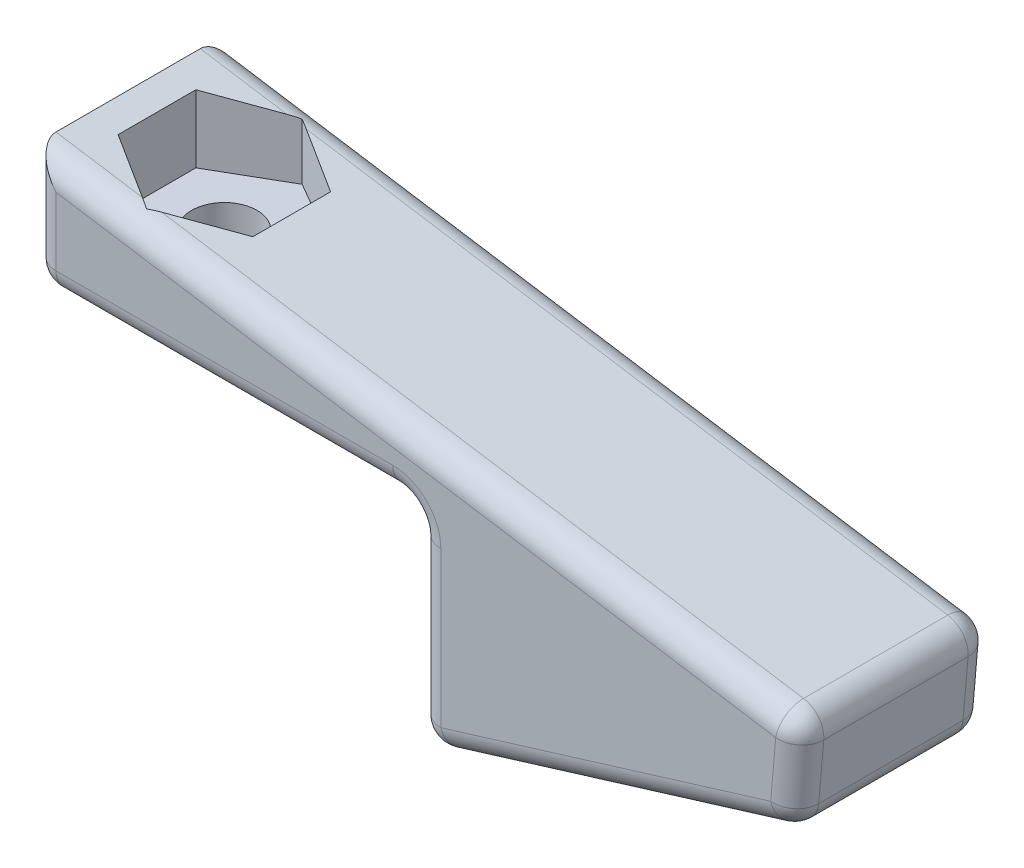
SolidWorks part; units mm, degrees
ref_plane "Front Plane" through (0, 0, 0) normal (0, 0, 1) x (1, 0, 0)
ref_plane "Top Plane" through (0, 0, 0) normal (0, 1, 0) x (1, 0, 0)
ref_plane "Right Plane" through (0, 0, 0) normal (1, 0, 0) x (0, 0, -1)
sketch "Sketch1" plane through (0, 0, 0) normal (0, 0, 1) x (1, 0, 0)
  line L0 (0, 0) -> (0, 7.9375)
  line L1 (0, 7.9375) -> (25.4, 3.9687)
  line L3 (50.2444, -6.35) -> (25.4, -13.97)
  line L4 (25.4, -13.97) -> (25.4, 0)
  line L5 (25.4, 0) -> (0, 0)
  line L6 (50.8, 0) -> (50.2444, -6.35)
  line L7 (50.8, 0) -> (25.4, 3.9687)
  point P3 (50.8, -1.5875)
  point P4 (49.4929, -7.9375)
  point P9 (0, 0)
  point P11 (0, 0)
  dimension "D1" = 7.9375
  dimension "D2" = 3.9687
  dimension "D3" = 25.4
  dimension "D4" = 13.97
  dimension "D5" = 5
  dimension "D6" = 6.35
  dimension "D7" = 50.8
extrude "Boss-Extrude1" add sketch "Sketch1" along normal mid plane 12.7
sketch "Sketch2" plane through (0, 0, 0) normal (0, -1, 0) x (-1, 0, 0)
  line L0 (0, -6.35) -> (0, 6.35) construction
  line L1 (-55, 0) -> (55, 0) construction
  circle A0 centre (-6.35, 0) radius 2.159
  dimension "D1" = 4.318
  dimension "D2" = 6.35
extrude "Cut-Extrude1" cut sketch "Sketch2" against normal up to next
sketch "Sketch3" plane through (0, 0, 0) normal (0, -1, 0) x (1, 0, 0)
  line L1 (6.35, 5.1326) -> (1.905, 2.5663)
  line L2 (1.905, 2.5663) -> (1.905, -2.5663)
  line L3 (1.905, -2.5663) -> (6.35, -5.1326)
  line L4 (6.35, -5.1326) -> (10.795, -2.5663)
  line L5 (10.795, -2.5663) -> (10.795, 2.5663)
  line L6 (10.795, 2.5663) -> (6.35, 5.1326)
  circle A0 centre (6.35, 0) radius 4.445 construction
  dimension "D1" = 8.89
extrude "Cut-Extrude2" cut sketch "Sketch3" against normal up to next from offset 3.175 offset against normal yes
sketch "Sketch4" plane through (25.4, 0, 0) normal (-1, 0, 0) x (0, 0, 1)
  line L0 (6.35, 0) -> (-6.35, 0) construction
  circle A0 centre (0, -7.62) radius 1.905
  dimension "D2" = 3.81
  dimension "D1" = 7.62
extrude "Cut-Extrude3" cut sketch "Sketch4" against normal blind 19.05
fillet "Fillet1" radius 1.5875 17 edges at (25.4, 0, 0) (25.4, -6.985, -6.35) (37.8222, -10.16, -6.35) (25.4, 3.9688, -6.35) (0, 3.9688, -6.35) (12.7, 0, -6.35) (0, 3.9688, 6.35) (25.4, 3.9688, 6.35) (37.8222, -10.16, 6.35) (25.4, -6.985, 6.35) (12.7, 0, 6.35) (0, 0, 0) (25.4, -13.97, 0) (50.5222, -3.175, -6.35) (50.5222, -3.175, 6.35) (50.2444, -6.35, 0) (50.8, 0, 0)
